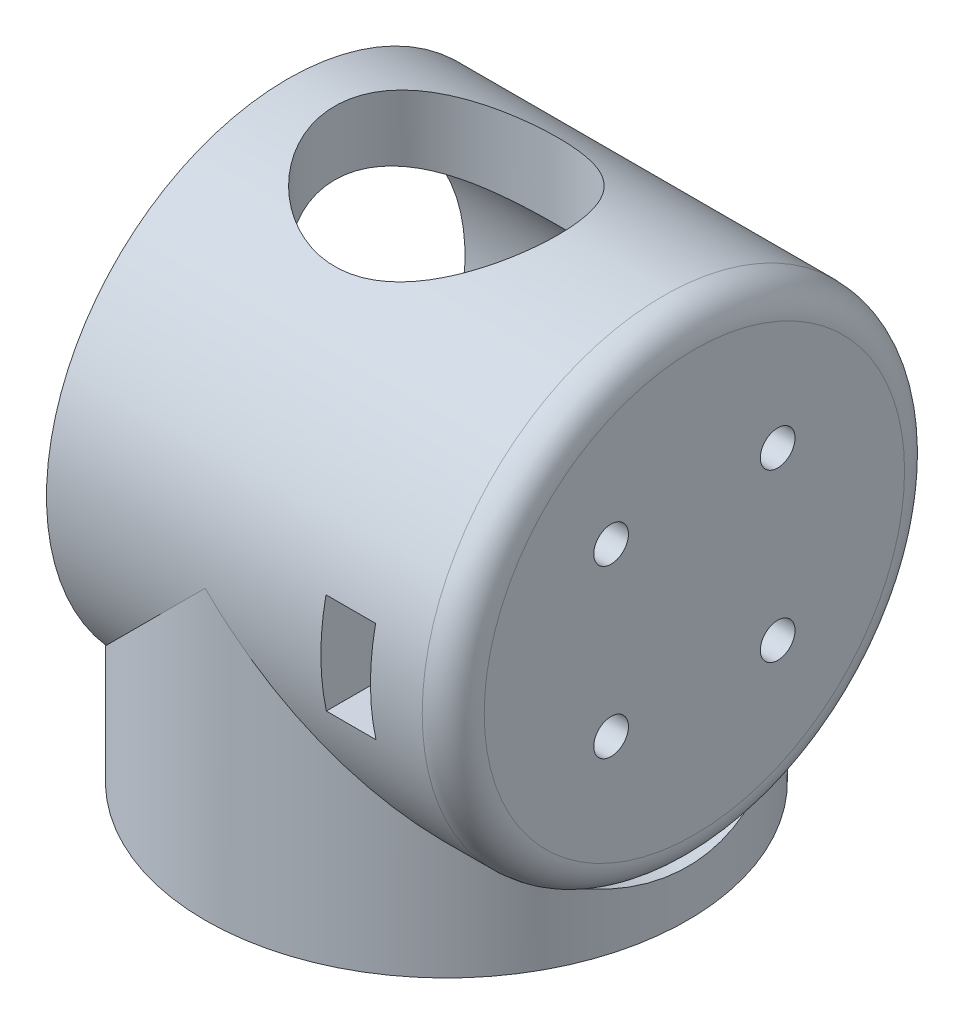
SolidWorks part; units mm, degrees
ref_plane "前视基准面" through (0, 0, 0) normal (0, 0, 1) x (1, 0, 0)
ref_plane "上视基准面" through (0, 0, 0) normal (0, 1, 0) x (1, 0, 0)
ref_plane "右视基准面" through (0, 0, 0) normal (1, 0, 0) x (0, 0, -1)
sketch "草图1" plane through (0, 0, 0) normal (0, 1, 0) x (1, 0, 0)
  circle A0 centre (0, 0) radius 28.4
  circle A1 centre (0, 0) radius 38.9
extrude "凸台-拉伸1" add sketch "草图1" along normal blind 46.39
sketch "草图2" plane through (0, 0, 0) normal (1, 0, 0) x (0, 0, -1)
  line L0 (0, 0) -> (0, 85.29) construction
  circle A0 centre (0, 46.39) radius 38.9
  circle A1 centre (0, 46.39) radius 39.39
  circle A2 centre (0, 46.39) radius 28.4
  point P3 (0, 46.39)
extrude "凸台-拉伸2" add sketch "草图2" along normal blind 40 and the other way blind 40 contours A2 | A0
sketch "草图3" plane through (0, 0, 0) normal (1, 0, 0) x (0, 0, -1)
  circle A0 centre (0, 46.39) radius 28.4
extrude "切除-拉伸1" cut sketch "草图3" against normal through all both and the other way through all
sketch "草图4" plane through (0, 0, 0) normal (0, 1, 0) x (1, 0, 0)
  circle A0 centre (0, 0) radius 28.4
extrude "切除-拉伸2" cut sketch "草图4" along normal up to next and the other way through all
sketch "草图5" plane through (0, 0, 0) normal (0, 1, 0) x (1, 0, 0)
  circle A0 centre (0, 0) radius 28.4
extrude "凸台-拉伸3" add sketch "草图5" along normal blind 10
sketch "草图6" plane through (0, 10, 0) normal (0, 1, 0) x (1, 0, 0)
  line L2 (13.5, 0) -> (6.75, 11.6913) construction
  line L3 (6.75, 11.6913) -> (-6.75, 11.6913) construction
  line L4 (-6.75, 11.6913) -> (-13.5, 0) construction
  line L5 (-13.5, 0) -> (-6.75, -11.6913) construction
  line L6 (-6.75, -11.6913) -> (6.75, -11.6913) construction
  line L7 (6.75, -11.6913) -> (13.5, 0) construction
  circle A1 centre (0, 0) radius 11.998 construction
  point P3 (-59.6527, 23.3032)
  point P4 (6.75, 11.6913)
  point P12 (13.5, 0)
  point P13 (6.75, -11.6913)
  point P14 (-6.75, -11.6913)
  point P15 (-13.5, 0)
  point P16 (-6.75, 11.6913)
hole_wizard "M3 六角头螺栓的柱形沉头孔1" positions "草图6" profile "草图7" counterbore size "M3" standard "GB" end condition through all
sketch "草图7" plane through (-6.75, 10, -11.6913) normal (1, 0, 0) x (0, 0, 1)
  line L0 (0, 0) -> (0, 10)
  line L1 (0, 10) -> (1.6, 10)
  line L3 (1.6, 10) -> (1.6, 4.5)
  line L4 (1.6, 4.5) -> (2.8, 4.5)
  line L5 (2.8, 4.5) -> (2.8, 0)
  line L7 (2.8, 0) -> (0, 0)
  line L11 (0, -6.35) -> (0, 107.95) construction
  dimension "通孔孔直径" = 3.2
  dimension "通孔孔深度" = 10
  dimension "柱形沉头孔直径" = 5.6
  dimension "柱形沉头孔深度" = 4.5
sketch "草图8" plane through (0, 0, 0) normal (1, 0, 0) x (0, 0, -1)
  circle A0 centre (0, 46.39) radius 28.4
extrude "凸台-拉伸4" add sketch "草图8" against normal blind 13.35 from offset 40
sketch "草图9" plane through (0, 0, 0) normal (0, 1, 0) x (1, 0, 0)
  line L0 (0, 0) -> (-8.15, 14.1162) construction
  circle A0 centre (-6.75, 11.6913) radius 2.8 construction
  circle A1 centre (-6.75, 11.6913) radius 2.8 construction
  circle A2 centre (0, 0) radius 18
extrude "切除-拉伸3" cut sketch "草图9" along normal up to next from offset 60
sketch "草图10" plane through (0, 0, 0) normal (0, 0, 1) x (1, 0, 0)
  line L0 (40, 46.39) -> (26.65, 46.39) construction
  line L1 (40, 7.49) -> (40, 85.29) construction
  line L2 (26.65, 46.39) -> (26.65, 38.1151)
  line L3 (26.65, 38.1151) -> (18.65, 38.1151)
  line L4 (18.65, 38.1151) -> (18.65, 46.39)
  line L5 (18.65, 46.39) -> (18.65, 54.39)
  line L6 (18.65, 54.39) -> (26.65, 54.39)
  line L7 (26.65, 54.39) -> (26.65, 46.39)
extrude "切除-拉伸4" cut sketch "草图10" against normal through all both and the other way through all
sketch "草图11" plane through (40, 0, 0) normal (1, 0, 0) x (0, 0, -1)
  line L1 (13.435, 59.825) -> (-13.435, 59.825) construction
  line L2 (-13.435, 59.825) -> (-13.435, 32.955) construction
  line L3 (-13.435, 32.955) -> (13.435, 32.955) construction
  line L4 (13.435, 32.955) -> (13.435, 59.825) construction
  circle A3 centre (0, 46.39) radius 19 construction
  circle A4 centre (0, 46.39) radius 13.435 construction
  point P36 (13.435, 59.825)
  point P39 (13.435, 32.955)
  point P42 (-13.435, 32.955)
  point P45 (-13.435, 59.825)
hole_wizard "M3 六角头螺栓的柱形沉头孔2" positions "草图11" profile "草图12" counterbore size "M3" standard "GB" end condition through all
sketch "草图12" plane through (40, 59.825, 13.435) normal (0, 1, 0) x (0, 0, -1)
  line L0 (0, 0) -> (0, 80)
  line L1 (0, 80) -> (1.6, 80)
  line L3 (1.6, 80) -> (1.6, 6.35)
  line L4 (1.6, 6.35) -> (2.8, 6.35)
  line L5 (2.8, 6.35) -> (2.8, 0)
  line L7 (2.8, 0) -> (0, 0)
  line L11 (0, -6.35) -> (0, 107.95) construction
  dimension "通孔孔直径" = 3.2
  dimension "通孔孔深度" = 80
  dimension "柱形沉头孔直径" = 5.6
  dimension "柱形沉头孔深度" = 6.35
sketch "草图13" plane through (0, 0, 0) normal (0, 0, 1) x (1, 0, 0)
  line L0 (40, 85.29) -> (40, 75.29) construction
  line L1 (40, 7.49) -> (40, 85.29) construction
  line L2 (40, 85.29) -> (30, 85.29) construction
  line L3 (40, 85.29) -> (18, 85.29) construction
  line L4 (30, 85.29) -> (40, 75.29) construction
  line L5 (35, 85.29) -> (40, 85.29)
  line L6 (40, 85.29) -> (40, 80.29)
  arc A0 (35, 85.29) -> (40, 80.29) centre (35, 80.29) cw
ref_axis "基准轴1" through (-40, 46.39, 0) along (1, 0, 0)
revolve "切除-旋转1" cut sketch "草图13" angle 360 about axis through (-40, 46.39, 0) along (1, 0, 0)
sketch "草图14" plane through (-40, 0, 0) normal (-1, 0, 0) x (0, 0, 1)
  circle A0 centre (0, 46.39) radius 38.9
extrude "切除-拉伸5" cut sketch "草图14" against normal blind 14.4 and the other way through all
sketch "草图15" plane through (0, 0, 0) normal (1, 0, 0) x (0, 0, -1)
  circle A0 centre (0, 46.39) radius 28.6
extrude "切除-拉伸6" cut sketch "草图15" along normal up to surface (26.65 mm away) from surface up to face at (26.65, 59.825, -15.035) starting at face at (-25.6, 46.39, 0)
